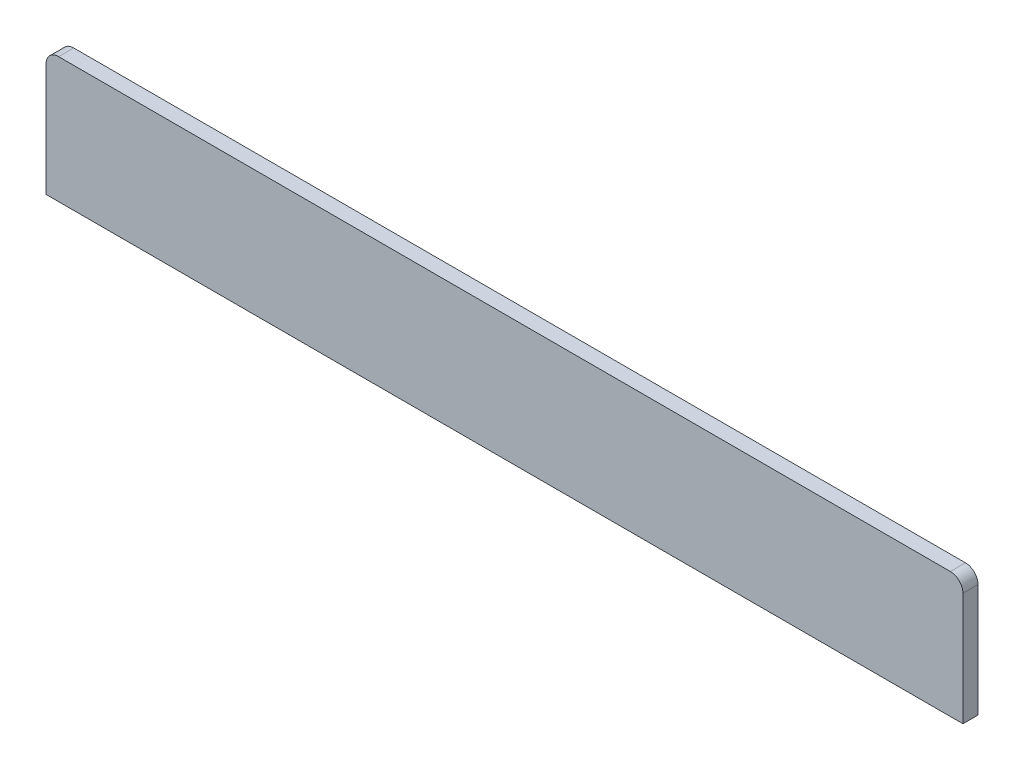
SolidWorks part; units mm, degrees
material "Клен"
ref_plane "Спереди" through (0, 0, 0) normal (0, 0, 1) x (1, 0, 0)
ref_plane "Сверху" through (0, 0, 0) normal (0, 1, 0) x (1, 0, 0)
ref_plane "Справа" through (0, 0, 0) normal (1, 0, 0) x (0, 0, -1)
sketch "Эскиз1" plane through (0, 0, 0) normal (0, 0, 1) x (1, 0, 0)
  line L1 (5, 0) -> (360, 0)
  line L2 (0, -5) -> (0, -50)
  line L3 (0, -50) -> (365, -50)
  line L4 (365, -5) -> (365, -50)
  arc A0 (360, 0) -> (365, -5) centre (360, -5) cw
  arc A1 (5, 0) -> (0, -5) centre (5, -5) ccw
  point P7 (365, 0)
  point P10 (0, 0)
  dimension "D3" = 5
  dimension "D1" = 365
  dimension "D2" = 50
extrude "Бобышка-Вытянуть1" add sketch "Эскиз1" along normal blind 6
